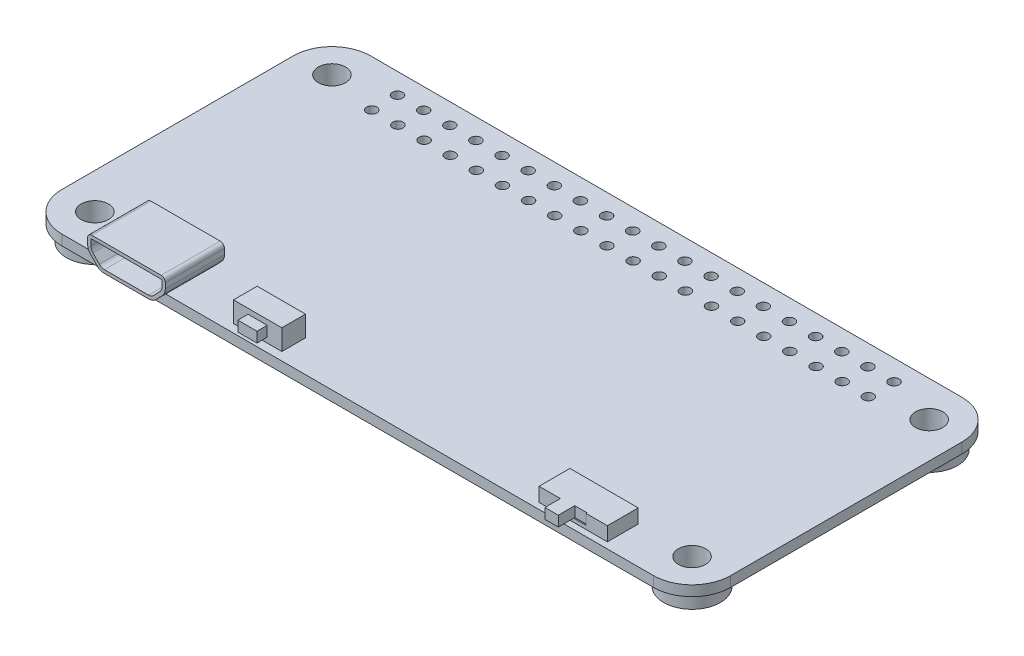
SolidWorks part; units mm, degrees
ref_plane "Front Plane" through (0, 0, 0) normal (0, 0, 1) x (1, 0, 0)
ref_plane "Top Plane" through (0, 0, 0) normal (0, 1, 0) x (1, 0, 0)
ref_plane "Right Plane" through (0, 0, 0) normal (1, 0, 0) x (0, 0, -1)
sketch "Sketch1" plane through (0, 0, 0) normal (0, 1, 0) x (1, 0, 0)
  line L1 (-28.75, 15) -> (28.75, 15)
  line L2 (-32.5, 11.25) -> (-32.5, -11.25)
  line L3 (-28.75, -15) -> (28.75, -15)
  line L4 (32.5, 11.25) -> (32.5, -11.25)
  line L5 (-32.5, 15) -> (32.5, -15) construction
  line L6 (-32.5, -15) -> (32.5, 15) construction
  arc A0 (-32.5, -11.25) -> (-28.75, -15) centre (-28.75, -11.25) ccw
  arc A1 (28.75, -15) -> (32.5, -11.25) centre (28.75, -11.25) ccw
  arc A2 (28.75, 15) -> (32.5, 11.25) centre (28.75, 11.25) cw
  arc A3 (-28.75, 15) -> (-32.5, 11.25) centre (-28.75, 11.25) ccw
  point P0 (0, 0)
  dimension "D3" = 3.75
  dimension "D1" = 65
  dimension "D2" = 30
extrude "Boss-Extrude1" add sketch "Sketch1" along normal blind 1 contours L1 A2 L4 A1 L3 A0 L2 A3
sketch "Sketch2" plane through (0, 1, 0) normal (0, 1, 0) x (1, 0, 0)
  line L0 (0, 15) -> (0, -15) construction
  line L1 (-28.75, 15) -> (28.75, 15) construction
  line L2 (-28.75, -15) -> (28.75, -15) construction
  line L3 (-32.5, 0) -> (32.5, 0) construction
  line L4 (-32.5, 11.25) -> (-32.5, -11.25) construction
  line L5 (32.5, 11.25) -> (32.5, -11.25) construction
  circle A0 centre (-29.025, 11.525) radius 1.325
  circle A2 centre (29.025, 11.525) radius 1.325
  circle A3 centre (29.025, -11.525) radius 1.325
  circle A4 centre (-29.025, -11.525) radius 1.325
  dimension "D1" = 2.65
  dimension "D2" = 2.15
  dimension "D3" = 2.15
extrude "Cut-Extrude1" cut sketch "Sketch2" against normal through all
sketch "Sketch3" plane through (0, 1, 0) normal (0, 1, 0) x (1, 0, 0)
  line L0 (-24.128, 13) -> (-24.128, 10.5) construction
  line L3 (-28.75, 15) -> (28.75, 15) construction
  line L5 (-32.5, 11.25) -> (-32.5, -11.25) construction
  circle A0 centre (-24.128, 13) radius 0.5
  circle A1 centre (-24.128, 10.5) radius 0.5
  dimension "D1" = 1
  dimension "D3" = 1.5
  dimension "D4" = 7.872
  dimension "D2" = 2.5
extrude "Cut-Extrude2" cut sketch "Sketch3" against normal through all
pattern_linear "LPattern1" count 20 spacing 2.54 along (1, 0, 0) of "Cut-Extrude2"
sketch "Sketch15" plane through (0, 0, 15) normal (0, 0, 1) x (1, 0, 0)
  line L0 (-21.225, 1) -> (-21.225, 3.6) construction
  line L1 (-28.75, 1) -> (28.75, 1) construction
  line L2 (-24.6, 3.6) -> (-17.85, 3.6)
  line L3 (-17.45, 3.2) -> (-17.45, 2.6523)
  line L4 (-17.7286, 1.9598) -> (-18.3548, 1.3075)
  line L5 (-19.0762, 1) -> (-23.3738, 1)
  line L7 (-24.7214, 1.9598) -> (-24.0952, 1.3075)
  line L8 (-25, 3.2) -> (-25, 2.6523)
  line L9 (15.325, 0) -> (15.325, 5.5788) construction
  line L10 (-28.75, 0) -> (28.75, 0) construction
  line L11 (-32.5, 1) -> (-32.5, 0) construction
  arc A0 (-18.3548, 1.3075) -> (-19.0762, 1) centre (-19.0762, 2) cw
  arc A1 (-24.0952, 1.3075) -> (-23.3738, 1) centre (-23.3738, 2) ccw
  arc A2 (-17.45, 2.6523) -> (-17.7286, 1.9598) centre (-18.45, 2.6523) cw
  arc A3 (-24.7214, 1.9598) -> (-25, 2.6523) centre (-24, 2.6523) cw
  arc A4 (-17.85, 3.6) -> (-17.45, 3.2) centre (-17.85, 3.2) cw
  arc A5 (-25, 3.2) -> (-24.6, 3.6) centre (-24.6, 3.2) cw
  point P14 (-18.65, 1)
  point P17 (-23.8, 1)
  point P20 (-17.45, 2.25)
  point P23 (-25, 2.25)
  point P26 (-17.45, 3.6)
  point P29 (-25, 3.6)
  dimension "D6" = 1
  dimension "D7" = 0.4
  dimension "D1" = 7.55
  dimension "D2" = 2.6
  dimension "D3" = 1.35
  dimension "D4" = 5.15
  dimension "D5" = 7.5
extrude "Boss-Extrude6" add sketch "Sketch15" along normal blind 1.25 and the other way blind 4.5
sketch "Sketch16" plane through (0, 0, 16.25) normal (0, 0, 1) x (1, 0, 0)
  line L30 (-18.5857, 1.5291) -> (-17.9595, 2.1814)
  line L31 (-17.77, 2.6523) -> (-17.77, 3.2)
  line L32 (-17.85, 3.28) -> (-24.6, 3.28)
  line L33 (-24.68, 3.2) -> (-24.68, 2.6523)
  line L34 (-24.4905, 2.1814) -> (-23.8643, 1.5291)
  line L35 (-23.3738, 1.32) -> (-19.0762, 1.32)
  line L36 (-18.5857, 1.5291) -> (-17.9595, 2.1814)
  line L37 (-17.77, 2.6523) -> (-17.77, 3.2)
  line L38 (-17.85, 3.28) -> (-24.6, 3.28)
  line L39 (-24.68, 3.2) -> (-24.68, 2.6523)
  line L40 (-24.4905, 2.1814) -> (-23.8643, 1.5291)
  line L41 (-23.3738, 1.32) -> (-19.0762, 1.32)
  arc A30 (-19.0762, 1.32) -> (-18.5857, 1.5291) centre (-19.0762, 2) ccw
  arc A31 (-17.9595, 2.1814) -> (-17.77, 2.6523) centre (-18.45, 2.6523) ccw
  arc A32 (-17.77, 3.2) -> (-17.85, 3.28) centre (-17.85, 3.2) ccw
  arc A33 (-24.6, 3.28) -> (-24.68, 3.2) centre (-24.6, 3.2) ccw
  arc A34 (-24.68, 2.6523) -> (-24.4905, 2.1814) centre (-24, 2.6523) ccw
  arc A35 (-23.8643, 1.5291) -> (-23.3738, 1.32) centre (-23.3738, 2) ccw
  arc A36 (-19.0762, 1.32) -> (-18.5857, 1.5291) centre (-19.0762, 2) ccw
  arc A37 (-17.9595, 2.1814) -> (-17.77, 2.6523) centre (-18.45, 2.6523) ccw
  arc A38 (-17.77, 3.2) -> (-17.85, 3.28) centre (-17.85, 3.2) ccw
  arc A39 (-24.6, 3.28) -> (-24.68, 3.2) centre (-24.6, 3.2) ccw
  arc A40 (-24.68, 2.6523) -> (-24.4905, 2.1814) centre (-24, 2.6523) ccw
  arc A41 (-23.8643, 1.5291) -> (-23.3738, 1.32) centre (-23.3738, 2) ccw
  dimension "D2" = 0.32
extrude "Cut-Extrude9" cut sketch "Sketch16" against normal blind 5.25
sketch "草图1" plane through (0, 1, 0) normal (0, 1, 0) x (1, 0, 0)
  line L0 (-32.5, 11.25) -> (-32.5, -11.25) construction
  line L1 (-12.87, -11.9) -> (-8.17, -11.9)
  line L2 (-12.87, -11.9) -> (-12.87, -14.2)
  line L3 (-12.87, -14.2) -> (-8.17, -14.2)
  line L4 (-8.17, -11.9) -> (-8.17, -14.2)
  line L5 (-28.75, -15) -> (-23.3738, -15) construction
  dimension "D1" = 4.7
  dimension "D2" = 2.3
  dimension "D3" = 19.63
  dimension "D4" = 0.8
extrude "凸台-拉伸1" add sketch "草图1" along normal blind 2
sketch "草图2" plane through (0, 0, 14.2) normal (0, 0, 1) x (1, 0, 0)
  line L0 (-12.87, 3) -> (-8.17, 3) construction
  line L5 (-11.45, 2.5) -> (-9.59, 2.5)
  line L6 (-11.45, 2.5) -> (-11.45, 1.5)
  line L7 (-11.45, 1.5) -> (-9.59, 1.5)
  line L8 (-9.59, 2.5) -> (-9.59, 1.5)
  line L9 (-11.45, 2.5) -> (-9.59, 1.5) construction
  line L10 (-11.45, 1.5) -> (-9.59, 2.5) construction
  line L11 (-8.17, 3) -> (-8.17, 1) construction
  point P0 (-10.52, 2)
  point P8 (-10.52, 3)
  point P12 (-8.17, 2)
  dimension "D1" = 1.86
  dimension "D2" = 1
extrude "凸台-拉伸2" add sketch "草图2" along normal blind 1
sketch "草图6" plane through (0, 1, 0) normal (0, 1, 0) x (1, 0, 0)
  line L0 (32.5, 11.25) -> (32.5, -11.25) construction
  line L1 (23.67, -11.4) -> (17.03, -11.4)
  line L2 (23.67, -11.4) -> (23.67, -14.4)
  line L3 (23.67, -14.4) -> (17.03, -14.4)
  line L4 (17.03, -11.4) -> (17.03, -14.4)
  line L5 (23.67, -11.4) -> (17.03, -14.4) construction
  line L6 (23.67, -14.4) -> (17.03, -11.4) construction
  line L7 (-19.0762, -15) -> (28.75, -15) construction
  point P0 (20.35, -12.9)
  dimension "D1" = 8.83
  dimension "D2" = 6.64
  dimension "D3" = 3
  dimension "D4" = 0.6
extrude "凸台-拉伸6" add sketch "草图6" along normal blind 1.36
sketch "草图7" plane through (0, 0, 14.4) normal (0, 0, 1) x (1, 0, 0)
  line L0 (17.03, 2.36) -> (23.67, 2.36) construction
  line L1 (19.1, 2.36) -> (21.6, 2.36)
  line L2 (19.1, 2.36) -> (19.1, 1.36)
  line L3 (19.1, 1.36) -> (21.6, 1.36)
  line L4 (21.6, 2.36) -> (21.6, 1.36)
  line L5 (23.67, 2.36) -> (17.03, 2.36) construction
  point P8 (20.35, 2.36)
  point P9 (20.35, 2.36)
  dimension "D1" = 1
  dimension "D2" = 2.5
extrude "切除-拉伸1" cut sketch "草图7" against normal blind 0.1
sketch "草图8" plane through (0, 0, 14.3) normal (0, 0, 1) x (1, 0, 0)
  line L0 (19.1, 2.36) -> (19.1, 1.36) construction
  line L1 (19.1, 2.36) -> (20.4, 2.36)
  line L2 (19.1, 2.36) -> (19.1, 1.36)
  line L3 (19.1, 1.36) -> (20.4, 1.36)
  line L4 (20.4, 2.36) -> (20.4, 1.36)
  line L5 (21.6, 2.36) -> (19.1, 2.36) construction
  line L6 (19.1, 1.36) -> (21.6, 1.36) construction
  dimension "D1" = 1.3
extrude "凸台-拉伸7" add sketch "草图8" along normal blind 1.6
sketch "草图9" plane through (0, 0, 0) normal (0, -1, 0) x (1, 0, 0)
  circle A0 centre (29.025, 11.525) radius 2.75
  circle A1 centre (29.025, -11.525) radius 2.75
  circle A2 centre (-29.025, 11.525) radius 2.75
  circle A3 centre (-29.025, -11.525) radius 2.75
  circle A4 centre (29.025, 11.525) radius 1.325 construction
  circle A5 centre (29.025, -11.525) radius 1.325 construction
  circle A6 centre (-29.025, 11.525) radius 1.325 construction
  circle A7 centre (-29.025, -11.525) radius 1.325 construction
  circle A8 centre (29.025, 11.525) radius 1.325
  circle A9 centre (29.025, -11.525) radius 1.325
  circle A10 centre (-29.025, 11.525) radius 1.325
  circle A11 centre (-29.025, -11.525) radius 1.325
  dimension "D1" = 5.5
extrude "凸台-拉伸8" add sketch "草图9" along normal blind 1.5
